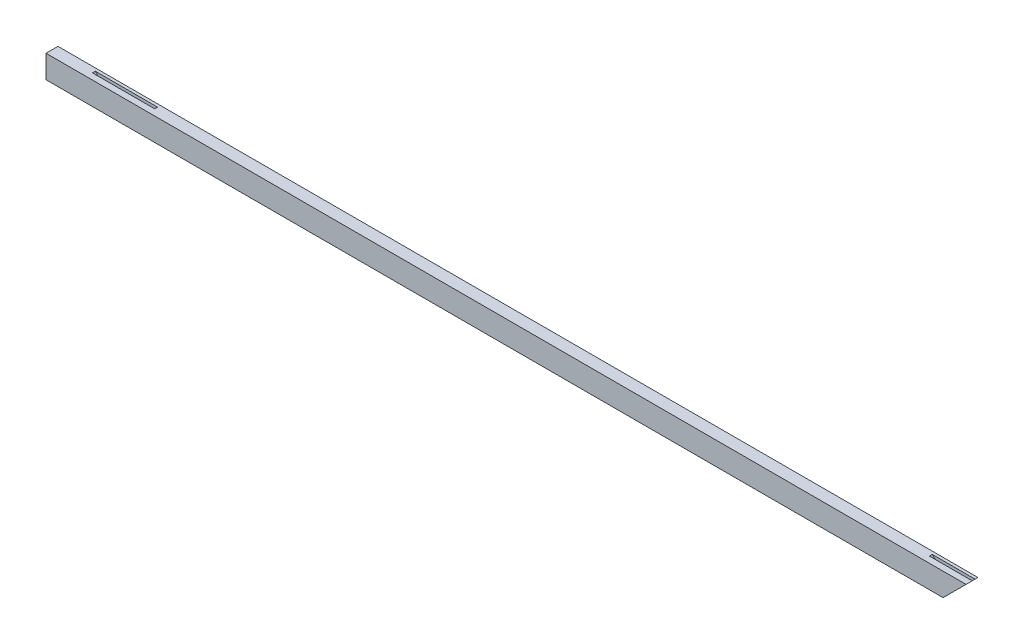
SolidWorks part; units mm, degrees
ref_plane "前视基准面" through (0, 0, 0) normal (0, 0, 1) x (1, 0, 0)
ref_plane "上视基准面" through (0, 0, 0) normal (0, 1, 0) x (1, 0, 0)
ref_plane "右视基准面" through (0, 0, 0) normal (1, 0, 0) x (0, 0, -1)
sketch "草图1" plane through (0, 0, 0) normal (0, 0, 1) x (1, 0, 0)
  line L0 (0, 24) -> (1922, 24)
  line L1 (1922, 24) -> (1874, -24)
  line L2 (1874, -24) -> (0, -24)
  line L3 (0, -24) -> (0, 24)
  point P2 (0, 0)
  dimension "D1" = 1922
  dimension "D2" = 48
  dimension "D3" = 45
extrude "凸台-拉伸1" add sketch "草图1" along normal blind 25
sketch "草图2" plane through (0, -24, 0) normal (0, -1, 0) x (1, 0, 0)
  line L0 (91.5, 12) -> (91.5, 6)
  line L1 (91.5, 6) -> (206.5, 6)
  line L2 (206.5, 6) -> (206.5, 12)
  line L3 (206.5, 12) -> (91.5, 12)
  line L4 (0, 0) -> (1874, 0) construction
  point P6 (149, 12)
  dimension "D1" = 115
  dimension "D2" = 6
  dimension "D3" = 6
  dimension "D4" = 1773
extrude "切除-拉伸1" cut sketch "草图2" against normal blind 7.5
draft "拔模1" type of draft neutral plane draft angle 45 faces to draft 2 face at (206.5, -20.25, 9) face at (91.5, -20.25, 9) neutral plane through (0, -16.5, 0) neutral plane normal (0, -1, 0) parameters "D1"=45
mirror "镜向1" about plane through (0, 0, 0) normal (0, 1, 0) of face at (149, -20.25, 12) of face at (210.25, -20.25, 9) of face at (149, -16.5, 9) of face at (87.75, -20.25, 9) of face at (149, -20.25, 6)
sketch "草图3" plane through (0, 0, 25) normal (0, 0, 1) x (1, 0, 0)
  line L0 (1832.5, 24) -> (1840, 16.5)
  line L1 (1922, 24) -> (0, 24) construction
  line L2 (1840, 16.5) -> (1914.5, 16.5)
  line L3 (1874, -24) -> (1922, 24) construction
  line L4 (1914.5, 16.5) -> (1922, 24)
  line L5 (1922, 24) -> (1832.5, 24)
  line L6 (1832.5, -24) -> (1840, -16.5)
  line L7 (0, -24) -> (1874, -24) construction
  line L8 (1840, -16.5) -> (1881.5, -16.5)
  line L9 (1881.5, -16.5) -> (1874, -24)
  line L10 (1874, -24) -> (1832.5, -24)
  dimension "D1" = 82
  dimension "D2" = 34
  dimension "D3" = 45
  dimension "D4" = 45
  dimension "D5" = 7.5
  dimension "D6" = 7.5
extrude "切除-拉伸2" cut sketch "草图3" against normal blind 6 from offset 13 offset against normal yes
